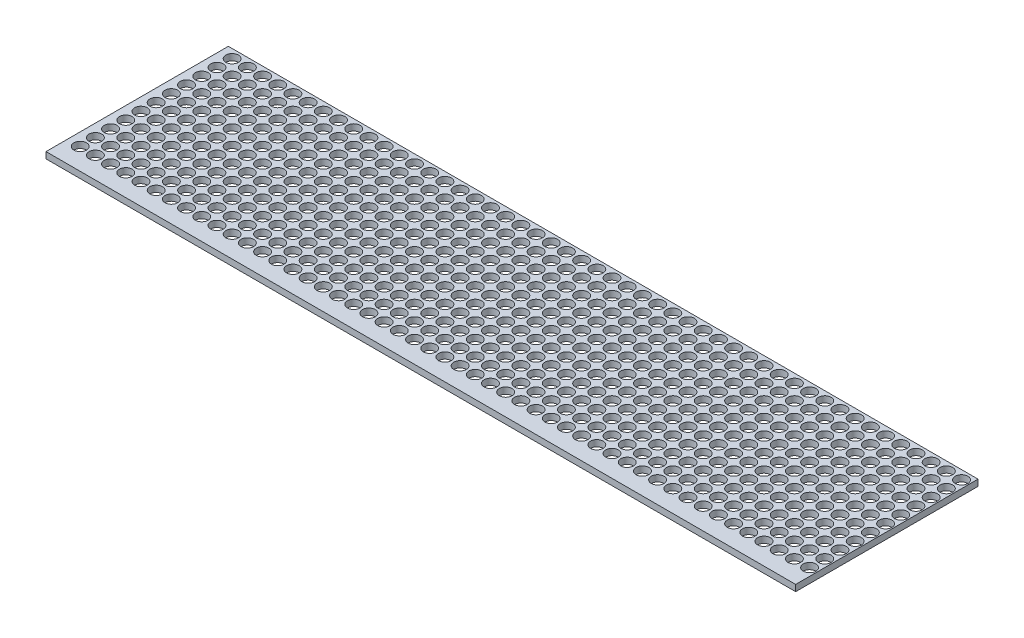
SolidWorks part; units mm, degrees
ref_plane "Front Plane" through (0, 0, 0) normal (0, 0, 1) x (1, 0, 0)
ref_plane "Top Plane" through (0, 0, 0) normal (0, 1, 0) x (1, 0, 0)
ref_plane "Right Plane" through (0, 0, 0) normal (1, 0, 0) x (0, 0, -1)
sketch "Sketch1" plane through (0, 0, 0) normal (0, 1, 0) x (1, 0, 0)
  line L1 (-296, 72) -> (296, 72)
  line L2 (-296, 72) -> (-296, -72)
  line L3 (-296, -72) -> (296, -72)
  line L4 (296, 72) -> (296, -72)
  line L5 (-296, 72) -> (296, -72) construction
  line L6 (-296, -72) -> (296, 72) construction
  point P0 (0, 0)
  dimension "D1" = 144
  dimension "D2" = 592
extrude "Boss-Extrude1" add sketch "Sketch1" along normal blind 5
sketch "Sketch2" plane through (0, 5, 0) normal (0, 1, 0) x (1, 0, 0)
  line L0 (-296, 72) -> (-296, -72) construction
  line L2 (296, 72) -> (-296, 72) construction
  circle A0 centre (-286, 65) radius 5
  circle A1 centre (-274, 65) radius 5
  circle A2 centre (-262, 65) radius 5
  circle A3 centre (-250, 65) radius 5
  circle A4 centre (-238, 65) radius 5
  circle A5 centre (-226, 65) radius 5
  circle A6 centre (-214, 65) radius 5
  circle A7 centre (-202, 65) radius 5
  circle A8 centre (-190, 65) radius 5
  circle A9 centre (-178, 65) radius 5
  circle A10 centre (-166, 65) radius 5
  circle A11 centre (-154, 65) radius 5
  circle A12 centre (-142, 65) radius 5
  circle A13 centre (-130, 65) radius 5
  circle A14 centre (-118, 65) radius 5
  circle A15 centre (-106, 65) radius 5
  circle A16 centre (-94, 65) radius 5
  circle A17 centre (-82, 65) radius 5
  circle A18 centre (-70, 65) radius 5
  circle A19 centre (-58, 65) radius 5
  circle A20 centre (-46, 65) radius 5
  circle A21 centre (-34, 65) radius 5
  circle A22 centre (-22, 65) radius 5
  circle A23 centre (-10, 65) radius 5
  circle A24 centre (2, 65) radius 5
  circle A25 centre (14, 65) radius 5
  circle A26 centre (26, 65) radius 5
  circle A27 centre (38, 65) radius 5
  circle A28 centre (50, 65) radius 5
  circle A29 centre (62, 65) radius 5
  circle A30 centre (74, 65) radius 5
  circle A31 centre (86, 65) radius 5
  circle A32 centre (98, 65) radius 5
  circle A33 centre (110, 65) radius 5
  circle A34 centre (122, 65) radius 5
  circle A35 centre (134, 65) radius 5
  circle A36 centre (146, 65) radius 5
  circle A37 centre (158, 65) radius 5
  circle A38 centre (170, 65) radius 5
  circle A39 centre (182, 65) radius 5
  circle A40 centre (194, 65) radius 5
  circle A41 centre (206, 65) radius 5
  circle A42 centre (218, 65) radius 5
  circle A43 centre (230, 65) radius 5
  circle A44 centre (242, 65) radius 5
  circle A45 centre (254, 65) radius 5
  circle A46 centre (266, 65) radius 5
  circle A47 centre (278, 65) radius 5
  circle A48 centre (290, 65) radius 5
  circle A49 centre (-274, 53) radius 5
  circle A50 centre (-262, 53) radius 5
  circle A51 centre (-250, 53) radius 5
  circle A52 centre (-238, 53) radius 5
  circle A53 centre (-226, 53) radius 5
  circle A54 centre (-214, 53) radius 5
  circle A55 centre (-202, 53) radius 5
  circle A56 centre (-190, 53) radius 5
  circle A57 centre (-178, 53) radius 5
  circle A58 centre (-166, 53) radius 5
  circle A59 centre (-154, 53) radius 5
  circle A60 centre (-142, 53) radius 5
  circle A61 centre (-130, 53) radius 5
  circle A62 centre (-118, 53) radius 5
  circle A63 centre (-106, 53) radius 5
  circle A64 centre (-94, 53) radius 5
  circle A65 centre (-82, 53) radius 5
  circle A66 centre (-70, 53) radius 5
  circle A67 centre (-58, 53) radius 5
  circle A68 centre (-46, 53) radius 5
  circle A69 centre (-34, 53) radius 5
  circle A70 centre (-22, 53) radius 5
  circle A71 centre (-10, 53) radius 5
  circle A72 centre (2, 53) radius 5
  circle A73 centre (14, 53) radius 5
  circle A74 centre (26, 53) radius 5
  circle A75 centre (38, 53) radius 5
  circle A76 centre (50, 53) radius 5
  circle A77 centre (62, 53) radius 5
  circle A78 centre (74, 53) radius 5
  circle A79 centre (86, 53) radius 5
  circle A80 centre (98, 53) radius 5
  circle A81 centre (110, 53) radius 5
  circle A82 centre (122, 53) radius 5
  circle A83 centre (134, 53) radius 5
  circle A84 centre (146, 53) radius 5
  circle A85 centre (158, 53) radius 5
  circle A86 centre (170, 53) radius 5
  circle A87 centre (182, 53) radius 5
  circle A88 centre (194, 53) radius 5
  circle A89 centre (206, 53) radius 5
  circle A90 centre (218, 53) radius 5
  circle A91 centre (230, 53) radius 5
  circle A92 centre (242, 53) radius 5
  circle A93 centre (254, 53) radius 5
  circle A94 centre (266, 53) radius 5
  circle A95 centre (278, 53) radius 5
  circle A96 centre (290, 53) radius 5
  circle A97 centre (-274, 41) radius 5
  circle A98 centre (-262, 41) radius 5
  circle A99 centre (-250, 41) radius 5
  circle A100 centre (-238, 41) radius 5
  circle A101 centre (-226, 41) radius 5
  circle A102 centre (-214, 41) radius 5
  circle A103 centre (-202, 41) radius 5
  circle A104 centre (-190, 41) radius 5
  circle A105 centre (-178, 41) radius 5
  circle A106 centre (-166, 41) radius 5
  circle A107 centre (-154, 41) radius 5
  circle A108 centre (-142, 41) radius 5
  circle A109 centre (-130, 41) radius 5
  circle A110 centre (-118, 41) radius 5
  circle A111 centre (-106, 41) radius 5
  circle A112 centre (-94, 41) radius 5
  circle A113 centre (-82, 41) radius 5
  circle A114 centre (-70, 41) radius 5
  circle A115 centre (-58, 41) radius 5
  circle A116 centre (-46, 41) radius 5
  circle A117 centre (-34, 41) radius 5
  circle A118 centre (-22, 41) radius 5
  circle A119 centre (-10, 41) radius 5
  circle A120 centre (2, 41) radius 5
  circle A121 centre (14, 41) radius 5
  circle A122 centre (26, 41) radius 5
  circle A123 centre (38, 41) radius 5
  circle A124 centre (50, 41) radius 5
  circle A125 centre (62, 41) radius 5
  circle A126 centre (74, 41) radius 5
  circle A127 centre (86, 41) radius 5
  circle A128 centre (98, 41) radius 5
  circle A129 centre (110, 41) radius 5
  circle A130 centre (122, 41) radius 5
  circle A131 centre (134, 41) radius 5
  circle A132 centre (146, 41) radius 5
  circle A133 centre (158, 41) radius 5
  circle A134 centre (170, 41) radius 5
  circle A135 centre (182, 41) radius 5
  circle A136 centre (194, 41) radius 5
  circle A137 centre (206, 41) radius 5
  circle A138 centre (218, 41) radius 5
  circle A139 centre (230, 41) radius 5
  circle A140 centre (242, 41) radius 5
  circle A141 centre (254, 41) radius 5
  circle A142 centre (266, 41) radius 5
  circle A143 centre (278, 41) radius 5
  circle A144 centre (290, 41) radius 5
  circle A145 centre (-274, 29) radius 5
  circle A146 centre (-262, 29) radius 5
  circle A147 centre (-250, 29) radius 5
  circle A148 centre (-238, 29) radius 5
  circle A149 centre (-226, 29) radius 5
  circle A150 centre (-214, 29) radius 5
  circle A151 centre (-202, 29) radius 5
  circle A152 centre (-190, 29) radius 5
  circle A153 centre (-178, 29) radius 5
  circle A154 centre (-166, 29) radius 5
  circle A155 centre (-154, 29) radius 5
  circle A156 centre (-142, 29) radius 5
  circle A157 centre (-130, 29) radius 5
  circle A158 centre (-118, 29) radius 5
  circle A159 centre (-106, 29) radius 5
  circle A160 centre (-94, 29) radius 5
  circle A161 centre (-82, 29) radius 5
  circle A162 centre (-70, 29) radius 5
  circle A163 centre (-58, 29) radius 5
  circle A164 centre (-46, 29) radius 5
  circle A165 centre (-34, 29) radius 5
  circle A166 centre (-22, 29) radius 5
  circle A167 centre (-10, 29) radius 5
  circle A168 centre (2, 29) radius 5
  circle A169 centre (14, 29) radius 5
  circle A170 centre (26, 29) radius 5
  circle A171 centre (38, 29) radius 5
  circle A172 centre (50, 29) radius 5
  circle A173 centre (62, 29) radius 5
  circle A174 centre (74, 29) radius 5
  circle A175 centre (86, 29) radius 5
  circle A176 centre (98, 29) radius 5
  circle A177 centre (110, 29) radius 5
  circle A178 centre (122, 29) radius 5
  circle A179 centre (134, 29) radius 5
  circle A180 centre (146, 29) radius 5
  circle A181 centre (158, 29) radius 5
  circle A182 centre (170, 29) radius 5
  circle A183 centre (182, 29) radius 5
  circle A184 centre (194, 29) radius 5
  circle A185 centre (206, 29) radius 5
  circle A186 centre (218, 29) radius 5
  circle A187 centre (230, 29) radius 5
  circle A188 centre (242, 29) radius 5
  circle A189 centre (254, 29) radius 5
  circle A190 centre (266, 29) radius 5
  circle A191 centre (278, 29) radius 5
  circle A192 centre (290, 29) radius 5
  circle A193 centre (-274, 17) radius 5
  circle A194 centre (-262, 17) radius 5
  circle A195 centre (-250, 17) radius 5
  circle A196 centre (-238, 17) radius 5
  circle A197 centre (-226, 17) radius 5
  circle A198 centre (-214, 17) radius 5
  circle A199 centre (-202, 17) radius 5
  circle A200 centre (-190, 17) radius 5
  circle A201 centre (-178, 17) radius 5
  circle A202 centre (-166, 17) radius 5
  circle A203 centre (-154, 17) radius 5
  circle A204 centre (-142, 17) radius 5
  circle A205 centre (-130, 17) radius 5
  circle A206 centre (-118, 17) radius 5
  circle A207 centre (-106, 17) radius 5
  circle A208 centre (-94, 17) radius 5
  circle A209 centre (-82, 17) radius 5
  circle A210 centre (-70, 17) radius 5
  circle A211 centre (-58, 17) radius 5
  circle A212 centre (-46, 17) radius 5
  circle A213 centre (-34, 17) radius 5
  circle A214 centre (-22, 17) radius 5
  circle A215 centre (-10, 17) radius 5
  circle A216 centre (2, 17) radius 5
  circle A217 centre (14, 17) radius 5
  circle A218 centre (26, 17) radius 5
  circle A219 centre (38, 17) radius 5
  circle A220 centre (50, 17) radius 5
  circle A221 centre (62, 17) radius 5
  circle A222 centre (74, 17) radius 5
  circle A223 centre (86, 17) radius 5
  circle A224 centre (98, 17) radius 5
  circle A225 centre (110, 17) radius 5
  circle A226 centre (122, 17) radius 5
  circle A227 centre (134, 17) radius 5
  circle A228 centre (146, 17) radius 5
  circle A229 centre (158, 17) radius 5
  circle A230 centre (170, 17) radius 5
  circle A231 centre (182, 17) radius 5
  circle A232 centre (194, 17) radius 5
  circle A233 centre (206, 17) radius 5
  circle A234 centre (218, 17) radius 5
  circle A235 centre (230, 17) radius 5
  circle A236 centre (242, 17) radius 5
  circle A237 centre (254, 17) radius 5
  circle A238 centre (266, 17) radius 5
  circle A239 centre (278, 17) radius 5
  circle A240 centre (290, 17) radius 5
  circle A241 centre (-274, 5) radius 5
  circle A242 centre (-262, 5) radius 5
  circle A243 centre (-250, 5) radius 5
  circle A244 centre (-238, 5) radius 5
  circle A245 centre (-226, 5) radius 5
  circle A246 centre (-214, 5) radius 5
  circle A247 centre (-202, 5) radius 5
  circle A248 centre (-190, 5) radius 5
  circle A249 centre (-178, 5) radius 5
  circle A250 centre (-166, 5) radius 5
  circle A251 centre (-154, 5) radius 5
  circle A252 centre (-142, 5) radius 5
  circle A253 centre (-130, 5) radius 5
  circle A254 centre (-118, 5) radius 5
  circle A255 centre (-106, 5) radius 5
  circle A256 centre (-94, 5) radius 5
  circle A257 centre (-82, 5) radius 5
  circle A258 centre (-70, 5) radius 5
  circle A259 centre (-58, 5) radius 5
  circle A260 centre (-46, 5) radius 5
  circle A261 centre (-34, 5) radius 5
  circle A262 centre (-22, 5) radius 5
  circle A263 centre (-10, 5) radius 5
  circle A264 centre (2, 5) radius 5
  circle A265 centre (14, 5) radius 5
  circle A266 centre (26, 5) radius 5
  circle A267 centre (38, 5) radius 5
  circle A268 centre (50, 5) radius 5
  circle A269 centre (62, 5) radius 5
  circle A270 centre (74, 5) radius 5
  circle A271 centre (86, 5) radius 5
  circle A272 centre (98, 5) radius 5
  circle A273 centre (110, 5) radius 5
  circle A274 centre (122, 5) radius 5
  circle A275 centre (134, 5) radius 5
  circle A276 centre (146, 5) radius 5
  circle A277 centre (158, 5) radius 5
  circle A278 centre (170, 5) radius 5
  circle A279 centre (182, 5) radius 5
  circle A280 centre (194, 5) radius 5
  circle A281 centre (206, 5) radius 5
  circle A282 centre (218, 5) radius 5
  circle A283 centre (230, 5) radius 5
  circle A284 centre (242, 5) radius 5
  circle A285 centre (254, 5) radius 5
  circle A286 centre (266, 5) radius 5
  circle A287 centre (278, 5) radius 5
  circle A288 centre (290, 5) radius 5
  circle A289 centre (-274, -7) radius 5
  circle A290 centre (-262, -7) radius 5
  circle A291 centre (-250, -7) radius 5
  circle A292 centre (-238, -7) radius 5
  circle A293 centre (-226, -7) radius 5
  circle A294 centre (-214, -7) radius 5
  circle A295 centre (-202, -7) radius 5
  circle A296 centre (-190, -7) radius 5
  circle A297 centre (-178, -7) radius 5
  circle A298 centre (-166, -7) radius 5
  circle A299 centre (-154, -7) radius 5
  circle A300 centre (-142, -7) radius 5
  circle A301 centre (-130, -7) radius 5
  circle A302 centre (-118, -7) radius 5
  circle A303 centre (-106, -7) radius 5
  circle A304 centre (-94, -7) radius 5
  circle A305 centre (-82, -7) radius 5
  circle A306 centre (-70, -7) radius 5
  circle A307 centre (-58, -7) radius 5
  circle A308 centre (-46, -7) radius 5
  circle A309 centre (-34, -7) radius 5
  circle A310 centre (-22, -7) radius 5
  circle A311 centre (-10, -7) radius 5
  circle A312 centre (2, -7) radius 5
  circle A313 centre (14, -7) radius 5
  circle A314 centre (26, -7) radius 5
  circle A315 centre (38, -7) radius 5
  circle A316 centre (50, -7) radius 5
  circle A317 centre (62, -7) radius 5
  circle A318 centre (74, -7) radius 5
  circle A319 centre (86, -7) radius 5
  circle A320 centre (98, -7) radius 5
  circle A321 centre (110, -7) radius 5
  circle A322 centre (122, -7) radius 5
  circle A323 centre (134, -7) radius 5
  circle A324 centre (146, -7) radius 5
  circle A325 centre (158, -7) radius 5
  circle A326 centre (170, -7) radius 5
  circle A327 centre (182, -7) radius 5
  circle A328 centre (194, -7) radius 5
  circle A329 centre (206, -7) radius 5
  circle A330 centre (218, -7) radius 5
  circle A331 centre (230, -7) radius 5
  circle A332 centre (242, -7) radius 5
  circle A333 centre (254, -7) radius 5
  circle A334 centre (266, -7) radius 5
  circle A335 centre (278, -7) radius 5
  circle A336 centre (290, -7) radius 5
  circle A337 centre (-274, -19) radius 5
  circle A338 centre (-262, -19) radius 5
  circle A339 centre (-250, -19) radius 5
  circle A340 centre (-238, -19) radius 5
  circle A341 centre (-226, -19) radius 5
  circle A342 centre (-214, -19) radius 5
  circle A343 centre (-202, -19) radius 5
  circle A344 centre (-190, -19) radius 5
  circle A345 centre (-178, -19) radius 5
  circle A346 centre (-166, -19) radius 5
  circle A347 centre (-154, -19) radius 5
  circle A348 centre (-142, -19) radius 5
  circle A349 centre (-130, -19) radius 5
  circle A350 centre (-118, -19) radius 5
  circle A351 centre (-106, -19) radius 5
  circle A352 centre (-94, -19) radius 5
  circle A353 centre (-82, -19) radius 5
  circle A354 centre (-70, -19) radius 5
  circle A355 centre (-58, -19) radius 5
  circle A356 centre (-46, -19) radius 5
  circle A357 centre (-34, -19) radius 5
  circle A358 centre (-22, -19) radius 5
  circle A359 centre (-10, -19) radius 5
  circle A360 centre (2, -19) radius 5
  circle A361 centre (14, -19) radius 5
  circle A362 centre (26, -19) radius 5
  circle A363 centre (38, -19) radius 5
  circle A364 centre (50, -19) radius 5
  circle A365 centre (62, -19) radius 5
  circle A366 centre (74, -19) radius 5
  circle A367 centre (86, -19) radius 5
  circle A368 centre (98, -19) radius 5
  circle A369 centre (110, -19) radius 5
  circle A370 centre (122, -19) radius 5
  circle A371 centre (134, -19) radius 5
  circle A372 centre (146, -19) radius 5
  circle A373 centre (158, -19) radius 5
  circle A374 centre (170, -19) radius 5
  circle A375 centre (182, -19) radius 5
  circle A376 centre (194, -19) radius 5
  circle A377 centre (206, -19) radius 5
  circle A378 centre (218, -19) radius 5
  circle A379 centre (230, -19) radius 5
  circle A380 centre (242, -19) radius 5
  circle A381 centre (254, -19) radius 5
  circle A382 centre (266, -19) radius 5
  circle A383 centre (278, -19) radius 5
  circle A384 centre (290, -19) radius 5
  circle A385 centre (-274, -31) radius 5
  circle A386 centre (-262, -31) radius 5
  circle A387 centre (-250, -31) radius 5
  circle A388 centre (-238, -31) radius 5
  circle A389 centre (-226, -31) radius 5
  circle A390 centre (-214, -31) radius 5
  circle A391 centre (-202, -31) radius 5
  circle A392 centre (-190, -31) radius 5
  circle A393 centre (-178, -31) radius 5
  circle A394 centre (-166, -31) radius 5
  circle A395 centre (-154, -31) radius 5
  circle A396 centre (-142, -31) radius 5
  circle A397 centre (-130, -31) radius 5
  circle A398 centre (-118, -31) radius 5
  circle A399 centre (-106, -31) radius 5
  circle A400 centre (-94, -31) radius 5
  circle A401 centre (-82, -31) radius 5
  circle A402 centre (-70, -31) radius 5
  circle A403 centre (-58, -31) radius 5
  circle A404 centre (-46, -31) radius 5
  circle A405 centre (-34, -31) radius 5
  circle A406 centre (-22, -31) radius 5
  circle A407 centre (-10, -31) radius 5
  circle A408 centre (2, -31) radius 5
  circle A409 centre (14, -31) radius 5
  circle A410 centre (26, -31) radius 5
  circle A411 centre (38, -31) radius 5
  circle A412 centre (50, -31) radius 5
  circle A413 centre (62, -31) radius 5
  circle A414 centre (74, -31) radius 5
  circle A415 centre (86, -31) radius 5
  circle A416 centre (98, -31) radius 5
  circle A417 centre (110, -31) radius 5
  circle A418 centre (122, -31) radius 5
  circle A419 centre (134, -31) radius 5
  circle A420 centre (146, -31) radius 5
  circle A421 centre (158, -31) radius 5
  circle A422 centre (170, -31) radius 5
  circle A423 centre (182, -31) radius 5
  circle A424 centre (194, -31) radius 5
  circle A425 centre (206, -31) radius 5
  circle A426 centre (218, -31) radius 5
  circle A427 centre (230, -31) radius 5
  circle A428 centre (242, -31) radius 5
  circle A429 centre (254, -31) radius 5
  circle A430 centre (266, -31) radius 5
  circle A431 centre (278, -31) radius 5
  circle A432 centre (290, -31) radius 5
  circle A433 centre (-274, -43) radius 5
  circle A434 centre (-262, -43) radius 5
  circle A435 centre (-250, -43) radius 5
  circle A436 centre (-238, -43) radius 5
  circle A437 centre (-226, -43) radius 5
  circle A438 centre (-214, -43) radius 5
  circle A439 centre (-202, -43) radius 5
  circle A440 centre (-190, -43) radius 5
  circle A441 centre (-178, -43) radius 5
  circle A442 centre (-166, -43) radius 5
  circle A443 centre (-154, -43) radius 5
  circle A444 centre (-142, -43) radius 5
  circle A445 centre (-130, -43) radius 5
  circle A446 centre (-118, -43) radius 5
  circle A447 centre (-106, -43) radius 5
  circle A448 centre (-94, -43) radius 5
  circle A449 centre (-82, -43) radius 5
  circle A450 centre (-70, -43) radius 5
  circle A451 centre (-58, -43) radius 5
  circle A452 centre (-46, -43) radius 5
  circle A453 centre (-34, -43) radius 5
  circle A454 centre (-22, -43) radius 5
  circle A455 centre (-10, -43) radius 5
  circle A456 centre (2, -43) radius 5
  circle A457 centre (14, -43) radius 5
  circle A458 centre (26, -43) radius 5
  circle A459 centre (38, -43) radius 5
  circle A460 centre (50, -43) radius 5
  circle A461 centre (62, -43) radius 5
  circle A462 centre (74, -43) radius 5
  circle A463 centre (86, -43) radius 5
  circle A464 centre (98, -43) radius 5
  circle A465 centre (110, -43) radius 5
  circle A466 centre (122, -43) radius 5
  circle A467 centre (134, -43) radius 5
  circle A468 centre (146, -43) radius 5
  circle A469 centre (158, -43) radius 5
  circle A470 centre (170, -43) radius 5
  circle A471 centre (182, -43) radius 5
  circle A472 centre (194, -43) radius 5
  circle A473 centre (206, -43) radius 5
  circle A474 centre (218, -43) radius 5
  circle A475 centre (230, -43) radius 5
  circle A476 centre (242, -43) radius 5
  circle A477 centre (254, -43) radius 5
  circle A478 centre (266, -43) radius 5
  circle A479 centre (278, -43) radius 5
  circle A480 centre (290, -43) radius 5
  circle A481 centre (-274, -55) radius 5
  circle A482 centre (-262, -55) radius 5
  circle A483 centre (-250, -55) radius 5
  circle A484 centre (-238, -55) radius 5
  circle A485 centre (-226, -55) radius 5
  circle A486 centre (-214, -55) radius 5
  circle A487 centre (-202, -55) radius 5
  circle A488 centre (-190, -55) radius 5
  circle A489 centre (-178, -55) radius 5
  circle A490 centre (-166, -55) radius 5
  circle A491 centre (-154, -55) radius 5
  circle A492 centre (-142, -55) radius 5
  circle A493 centre (-130, -55) radius 5
  circle A494 centre (-118, -55) radius 5
  circle A495 centre (-106, -55) radius 5
  circle A496 centre (-94, -55) radius 5
  circle A497 centre (-82, -55) radius 5
  circle A498 centre (-70, -55) radius 5
  circle A499 centre (-58, -55) radius 5
  circle A500 centre (-46, -55) radius 5
  circle A501 centre (-34, -55) radius 5
  circle A502 centre (-22, -55) radius 5
  circle A503 centre (-10, -55) radius 5
  circle A504 centre (2, -55) radius 5
  circle A505 centre (14, -55) radius 5
  circle A506 centre (26, -55) radius 5
  circle A507 centre (38, -55) radius 5
  circle A508 centre (50, -55) radius 5
  circle A509 centre (62, -55) radius 5
  circle A510 centre (74, -55) radius 5
  circle A511 centre (86, -55) radius 5
  circle A512 centre (98, -55) radius 5
  circle A513 centre (110, -55) radius 5
  circle A514 centre (122, -55) radius 5
  circle A515 centre (134, -55) radius 5
  circle A516 centre (146, -55) radius 5
  circle A517 centre (158, -55) radius 5
  circle A518 centre (170, -55) radius 5
  circle A519 centre (182, -55) radius 5
  circle A520 centre (194, -55) radius 5
  circle A521 centre (206, -55) radius 5
  circle A522 centre (218, -55) radius 5
  circle A523 centre (230, -55) radius 5
  circle A524 centre (242, -55) radius 5
  circle A525 centre (254, -55) radius 5
  circle A526 centre (266, -55) radius 5
  circle A527 centre (278, -55) radius 5
  circle A528 centre (290, -55) radius 5
  circle A529 centre (-286, 53) radius 5
  circle A530 centre (-286, 41) radius 5
  circle A531 centre (-286, 29) radius 5
  circle A532 centre (-286, 17) radius 5
  circle A533 centre (-286, 5) radius 5
  circle A534 centre (-286, -7) radius 5
  circle A535 centre (-286, -19) radius 5
  circle A536 centre (-286, -31) radius 5
  circle A537 centre (-286, -43) radius 5
  circle A538 centre (-286, -55) radius 5
  dimension "D1" = 10
  dimension "D2" = 10
  dimension "D3" = 7
  dimension "D4" = 49
  dimension "D5" = 11
extrude "Cut-Extrude1" cut sketch "Sketch2" against normal blind 5
